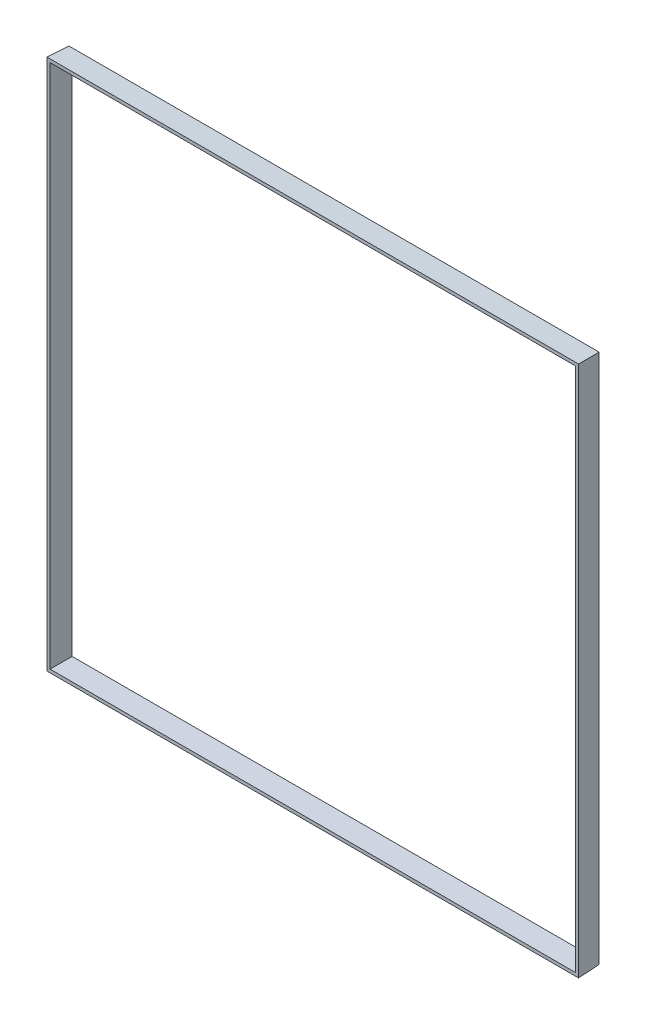
SolidWorks part; units mm, degrees
material "Rubber"
ref_plane "Front Plane" through (0, 0, 0) normal (0, 0, 1) x (1, 0, 0)
ref_plane "Top Plane" through (0, 0, 0) normal (0, 1, 0) x (1, 0, 0)
ref_plane "Right Plane" through (0, 0, 0) normal (1, 0, 0) x (0, 0, -1)
sketch "Sketch2" plane through (0, 0, 0) normal (0, 0, 1) x (1, 0, 0)
  line L1 (-124.35, -124.35) -> (124.35, -124.35)
  line L2 (-124.35, -124.35) -> (-124.35, 124.35)
  line L3 (-124.35, 124.35) -> (124.35, 124.35)
  line L4 (124.35, -124.35) -> (124.35, 124.35)
  line L5 (-124.35, -124.35) -> (124.35, 124.35) construction
  line L6 (-124.35, 124.35) -> (124.35, -124.35) construction
  point P0 (0, 0)
  dimension "D2" = 248.7
extrude "Boss-Extrude1" add sketch "Sketch2" against normal blind 9.98 draft 2
sketch "Sketch3" plane through (0, 0, 0) normal (0, 0, 1) x (1, 0, 0)
  line L0 (124.35, 124.35) -> (-124.35, 124.35) construction
  line L1 (-122.85, -122.85) -> (122.85, -122.85)
  line L2 (-122.85, -122.85) -> (-122.85, 122.85)
  line L3 (-122.85, 122.85) -> (122.85, 122.85)
  line L4 (122.85, -122.85) -> (122.85, 122.85)
  line L5 (-122.85, -122.85) -> (122.85, 122.85) construction
  line L6 (-122.85, 122.85) -> (122.85, -122.85) construction
  line L7 (-124.35, 124.35) -> (-124.35, -124.35) construction
  point P0 (0, 0)
  dimension "D1" = 1.5
  dimension "D2" = 1.5
extrude "Cut-Extrude1" cut sketch "Sketch3" against normal through all both draft 2 and the other way through all
